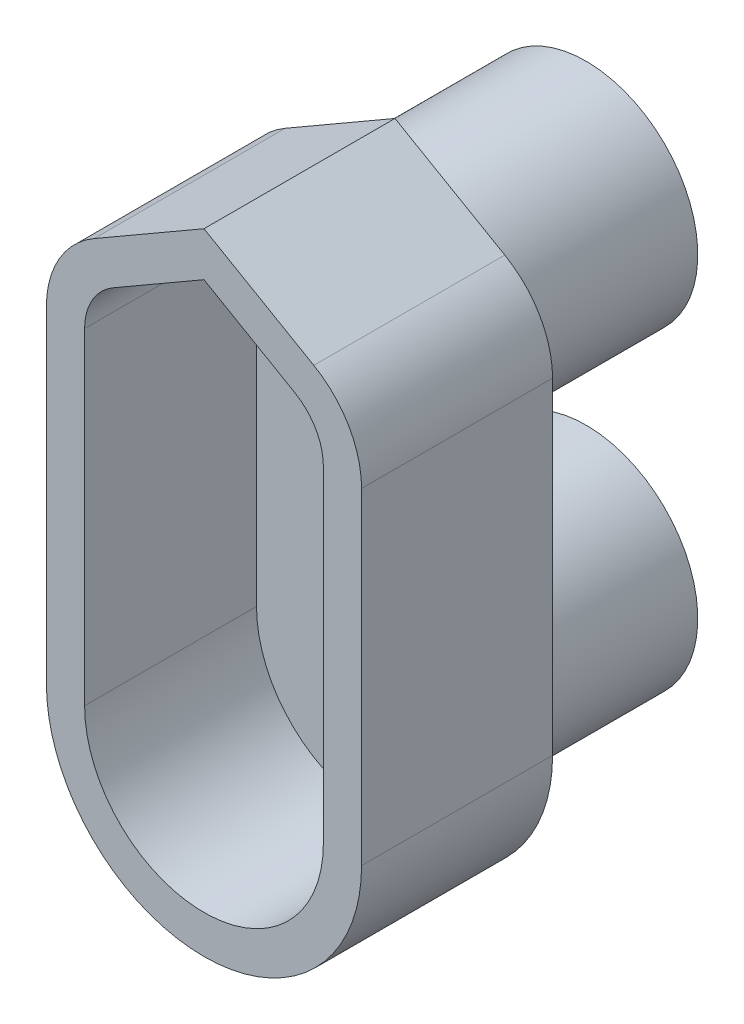
SolidWorks part; units mm, degrees
ref_plane "Ebene vorne" through (0, 0, 0) normal (0, 0, 1) x (1, 0, 0)
ref_plane "Ebene oben" through (0, 0, 0) normal (0, 1, 0) x (1, 0, 0)
ref_plane "Ebene rechts" through (0, 0, 0) normal (1, 0, 0) x (0, 0, -1)
sketch "Sketch1" plane through (0, 0, 0) normal (0, 0, 1) x (1, 0, 0)
  line L1 (0, 0) -> (-165, 0) construction
  line L2 (0, 0) -> (0, 165) construction
  line L3 (0, 165) -> (-165, 165) construction
  line L4 (-165, 0) -> (-165, 165) construction
  line L21 (-26.8644, 165) -> (-10.3644, 165)
  line L22 (-26.8644, 165) -> (-26.8644, 132)
  line L23 (-26.8644, 132) -> (-10.3644, 132)
  line L24 (-10.3644, 165) -> (-10.3644, 132)
  dimension "D1" = 165
  dimension "D2" = 165
  dimension "D14" = 33
  dimension "D15" = 16.5
extrude "Boss-Extrude1" add sketch "Sketch1" along normal blind 20
fillet "Fillet1" radius 8.25 2 edges at (-26.8644, 132, 10) (-10.3644, 132, 10)
chamfer "Chamfer1" distance 8.25 angle 30 2 edges at (-26.8644, 165, 10) (-10.3644, 165, 10)
sketch "Sketch2" plane through (0, 0, 0) normal (0, 0, -1) x (-1, 0, 0)
  line L0 (10.3644, 148.5) -> (26.8644, 148.5) construction
  line L5 (10.3644, 165) -> (26.8644, 165)
  line L6 (10.3644, 165) -> (10.3644, 132)
  line L7 (10.3644, 132) -> (26.8644, 132)
  line L8 (26.8644, 165) -> (26.8644, 132)
  circle A0 centre (18.6144, 156.75) radius 5.85
  circle A3 centre (18.6144, 156.75) radius 5.05
  circle A4 centre (18.6144, 140.25) radius 5.85
  circle A5 centre (18.6144, 140.25) radius 5.05
  point P15 (18.6144, 165)
  point P16 (18.6144, 132)
  dimension "D1" = 11.7
  dimension "D2" = 8.25
  dimension "D3" = 10.1
  dimension "D4" = 16.5
  dimension "D5" = 8.25
  dimension "D6" = 16.5
extrude "Cut-Extrude1" cut sketch "Sketch2" against normal blind 10
fillet "Fillet2" radius 5 2 edges at (-10.3644, 160.2369, 15) (-26.8644, 160.2369, 15)
sketch "Sketch3" plane through (0, 0, 20) normal (0, 0, 1) x (1, 0, 0)
  line L0 (-26.8644, 157.3501) -> (-26.8644, 140.25) construction
  line L1 (-26.8644, 132) -> (-10.3644, 132) construction
  line L2 (-26.8644, 132) -> (-26.8644, 165) construction
  line L3 (-26.8644, 165) -> (-10.3644, 165) construction
  line L4 (-10.3644, 132) -> (-10.3644, 165) construction
  line L5 (-26.8644, 148.5) -> (-10.3644, 148.5) construction
  circle A0 centre (-18.6144, 156.75) radius 2.5
  circle A1 centre (-18.6144, 140.25) radius 2.5
  point P6 (-18.6144, 132)
  point P8 (-18.6144, 165)
  dimension "D1" = 5
  dimension "D2" = 8.25
extrude "Cut-Extrude2" [suppressed] cut sketch "Sketch3" against normal blind 5
sketch "Sketch4" plane through (0, 0, 10) normal (0, 0, -1) x (-1, 0, 0)
  circle A0 centre (18.6144, 156.75) radius 5.1
  circle A1 centre (18.6144, 140.25) radius 5.1
  dimension "D1" = 10.2
  dimension "D2" = 10.2
extrude "Boss-Extrude2" add sketch "Sketch4" along normal blind 7.3
sketch "Skizze1" plane through (0, 0, 20) normal (0, 0, 1) x (1, 0, 0)
  line L8 (-12.3644, 140.25) -> (-12.3644, 157.3501)
  line L9 (-13.8644, 159.9482) -> (-18.6144, 162.6906)
  line L10 (-18.6144, 162.6906) -> (-23.3644, 159.9482)
  line L11 (-24.8644, 157.3501) -> (-24.8644, 140.25)
  line L12 (-12.3644, 140.25) -> (-12.3644, 157.3501)
  line L13 (-13.8644, 159.9482) -> (-18.6144, 162.6906)
  line L14 (-18.6144, 162.6906) -> (-23.3644, 159.9482)
  line L15 (-24.8644, 157.3501) -> (-24.8644, 140.25)
  arc A8 (-12.3644, 157.3501) -> (-13.8644, 159.9482) centre (-15.3644, 157.3501) ccw
  arc A9 (-23.3644, 159.9482) -> (-24.8644, 157.3501) centre (-21.8644, 157.3501) ccw
  arc A10 (-24.8644, 140.25) -> (-18.6144, 134) centre (-18.6144, 140.25) ccw
  arc A11 (-18.6144, 134) -> (-12.3644, 140.25) centre (-18.6144, 140.25) ccw
  arc A12 (-12.3644, 157.3501) -> (-13.8644, 159.9482) centre (-15.3644, 157.3501) ccw
  arc A13 (-23.3644, 159.9482) -> (-24.8644, 157.3501) centre (-21.8644, 157.3501) ccw
  arc A14 (-24.8644, 140.25) -> (-18.6144, 134) centre (-18.6144, 140.25) ccw
  arc A15 (-18.6144, 134) -> (-12.3644, 140.25) centre (-18.6144, 140.25) ccw
  dimension "D1" = 2
extrude "Schnitt-Linear austragen1" cut sketch "Skizze1" against normal blind 9
